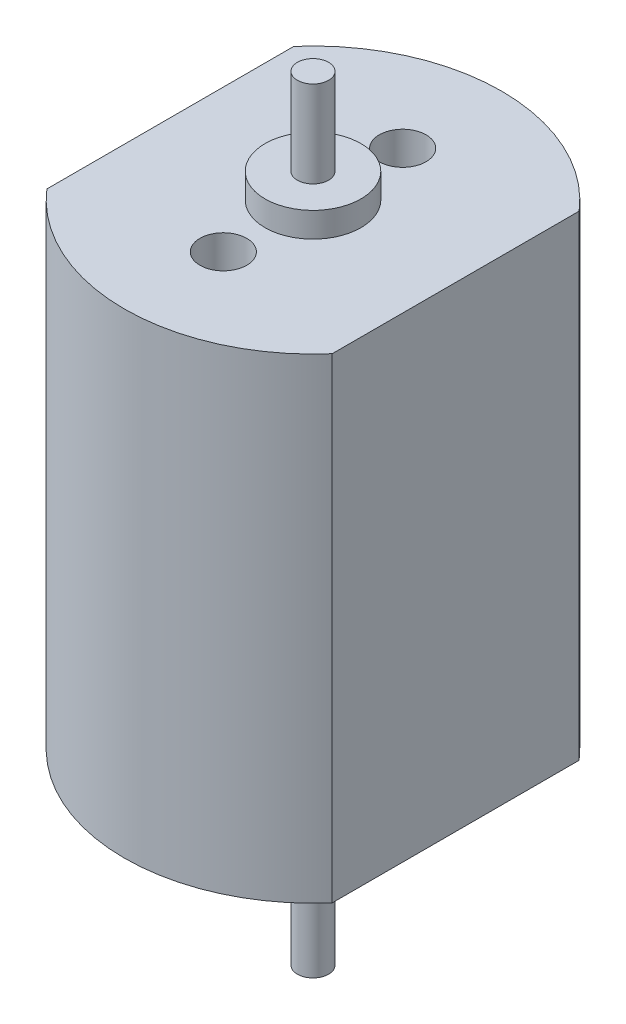
SolidWorks part; units mm, degrees
ref_plane "Front Plane" through (0, 0, 0) normal (0, 0, 1) x (1, 0, 0)
ref_plane "Top Plane" through (0, 0, 0) normal (0, 1, 0) x (1, 0, 0)
ref_plane "Right Plane" through (0, 0, 0) normal (1, 0, 0) x (0, 0, -1)
sketch "Sketch1" plane through (0, 0, 0) normal (0, 1, 0) x (1, 0, 0)
  line L4 (-9.15, 7.9175) -> (-9.15, -7.9175)
  line L5 (9.15, 7.9175) -> (9.15, -7.9175)
  arc A0 (9.15, 7.9175) -> (-9.15, 7.9175) centre (0, 0) ccw
  arc A1 (-9.15, -7.9175) -> (9.15, -7.9175) centre (0, 0) ccw
  circle A2 centre (0, 0) radius 1.03 construction
  dimension "D1" = 24.2
  dimension "D3" = 2.06
  dimension "D2" = 18.3
extrude "Boss-Extrude1" add sketch "Sketch1" along normal blind 30.5
sketch "Sketch2" plane through (0, 30.5, 0) normal (0, 1, 0) x (1, 0, 0)
  circle A0 centre (0, 0) radius 3.075
  circle A1 centre (0, 0) radius 1
  dimension "D1" = 6.15
  dimension "D2" = 2
extrude "Boss-Extrude2" add sketch "Sketch2" along normal blind 1.6
extrude "Boss-Extrude3" add sketch "Sketch2<2>" along normal blind 7.15 contours A1 region at (0, 30.5, 0)
sketch "Sketch2<2>" plane through (0, 30.5, 0) normal (0, 1, 0) x (1, 0, 0) same geometry as "Sketch2"
sketch "Sketch3" plane through (0, 0, 0) normal (0, -1, 0) x (1, 0, 0)
  circle A0 centre (0, 0) radius 4
  circle A1 centre (0, 0) radius 1
  dimension "D1" = 8
  dimension "D2" = 2
extrude "Boss-Extrude4" add sketch "Sketch3" along normal blind 2
extrude "Boss-Extrude5" add sketch "Sketch3<2>" along normal blind 12 contours A1 region at (0, 0, 0)
sketch "Sketch3<2>" plane through (0, 0, 0) normal (0, -1, 0) x (1, 0, 0) same geometry as "Sketch3"
sketch "Sketch4" plane through (0, 30.5, 0) normal (0, 1, 0) x (1, 0, 0)
  line L0 (0, -5.75) -> (0, 5.75) construction
  circle A0 centre (0, 5.75) radius 1.5
  circle A1 centre (0, -5.75) radius 1.5
  point P2 (0, 0)
  dimension "D2" = 3
  dimension "D1" = 11.5
extrude "Cut-Extrude1" cut sketch "Sketch4" against normal blind 5
